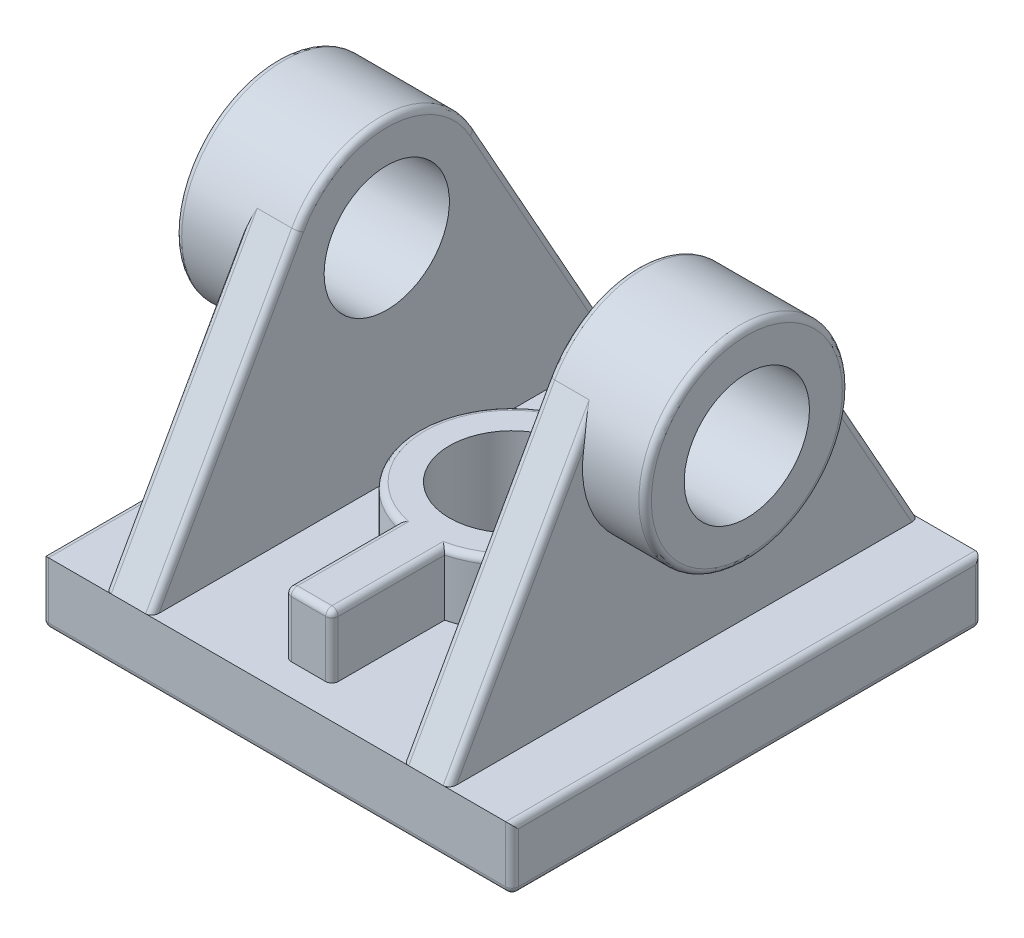
SolidWorks part; units mm, degrees
ref_plane "前视基准面" through (0, 0, 0) normal (0, 0, 1) x (1, 0, 0)
ref_plane "上视基准面" through (0, 0, 0) normal (0, 1, 0) x (1, 0, 0)
ref_plane "右视基准面" through (0, 0, 0) normal (1, 0, 0) x (0, 0, -1)
sketch "草图1" plane through (0, 0, 0) normal (0, 1, 0) x (1, 0, 0)
  line L0 (7.5, 7.5) -> (7.5, -7.5)
  line L1 (7.5, 7.5) -> (-7.5, 7.5)
  line L2 (7.5, -7.5) -> (-7.5, -7.5)
  line L3 (-7.5, 7.5) -> (-7.5, -7.5)
  line L4 (7.5, 7.5) -> (-7.5, -7.5) construction
  line L5 (7.5, -7.5) -> (-7.5, 7.5) construction
  point P1 (0, 0)
  dimension "D1" = 15
  dimension "D2" = 15
extrude "凸台-拉伸1" add sketch "草图1" along normal blind 2
sketch "草图2" plane through (0, 0, 0) normal (1, 0, 0) x (0, 0, -1)
  line L0 (0, 0) -> (0, 8.75) construction
  line L1 (-7.5, 2) -> (7.5, 2)
  line L2 (7.5, 2) -> (2.8364, 10.3367)
  line L3 (-7.5, 2) -> (-2.8364, 10.3367)
  arc A0 (2.8364, 10.3367) -> (-2.8364, 10.3367) centre (0, 8.75) ccw
  dimension "D2" = 6.5
  dimension "D1" = 8.75
extrude "凸台-拉伸2" add sketch "草图2" along normal blind 1.5 from offset 4
sketch "草图3" plane through (5.5, 0, 0) normal (1, 0, 0) x (0, 0, -1)
  circle A0 centre (0, 8.75) radius 3.25
  dimension "D1" = 6.5
extrude "凸台-拉伸3" add sketch "草图3" along normal blind 2
sketch "草图4" plane through (7.5, 0, 0) normal (1, 0, 0) x (0, 0, -1)
  circle A0 centre (0, 8.75) radius 2
  dimension "D1" = 4
extrude "切除-拉伸1" cut sketch "草图4" against normal up to next
mirror "镜向1" about plane through (0, 0, 0) normal (1, 0, 0) of "切除-拉伸1", "凸台-拉伸3", "凸台-拉伸2"
sketch "草图5" plane through (0, 2, 0) normal (0, 1, 0) x (1, 0, 0)
  line L0 (0.75, 6.5) -> (-0.75, 6.5)
  line L1 (0.75, 6.5) -> (0.75, 2.9047)
  line L2 (-0.75, 6.5) -> (-0.75, 2.9047)
  line L3 (0.75, -6.5) -> (-0.75, -6.5)
  line L4 (0.75, 6.5) -> (-0.75, -6.5) construction
  line L5 (-0.75, 6.5) -> (0.75, -6.5) construction
  line L6 (-0.75, -2.9047) -> (-0.75, -6.5)
  line L7 (0.75, -2.9047) -> (0.75, -6.5)
  arc A0 (-0.75, 2.9047) -> (-0.75, -2.9047) centre (0, 0) ccw
  arc A1 (0.75, -2.9047) -> (0.75, 2.9047) centre (0, 0) ccw
  dimension "D1" = 6
  dimension "D2" = 1.5
  dimension "D3" = 13
extrude "凸台-拉伸4" add sketch "草图5" along normal blind 2
sketch "草图6" plane through (0, 4, 0) normal (0, 1, 0) x (1, 0, 0)
  circle A0 centre (0, 0) radius 2
  dimension "D1" = 4
extrude "切除-拉伸2" cut sketch "草图6" against normal up to next
fillet "圆角3" radius 0.2 8 edges at (7.5, 1, 7.5) (7.5, 2, 0) (7.5, 1, -7.5) (7.5, 0, 0) (-7.5, 1, -7.5) (-7.5, 2, 0) (-7.5, 1, 7.5) (-7.5, 0, 0)
fillet "圆角4" radius 0.2 6 edges at (-7.4414, 0.0586, 7.4414) (7.4414, 0.0586, 7.4414) (7.4414, 0.0586, -7.4414) (-7.4414, 0.0586, -7.4414) (0, 0, 7.5) (0, 0, -7.5)
fillet "圆角6" radius 0.2 12 edges at (-4, 6.1683, -5.1682) (-4, 12, 0) (4, 12, 0) (-5.5, 6.1683, -5.1682) (-7.5, 8.75, -3.25) (-5.5, 6.1683, 5.1682) (-4, 6.1683, 5.1682) (7.5, 8.75, -3.25)
fillet "圆角7" radius 0.2 12 edges at (0.75, 3, -6.5) (0, 4, -6.5) (-0.75, 3, -6.5) (-0.75, 4, -4.7024) (0.75, 4, -4.7024) (0.75, 3, 6.5) (-0.75, 3, 6.5) (0, 4, 6.5) (-0.75, 4, 4.7024) (0.75, 4, 4.7024) (-3, 4, 0) (3, 4, 0)
